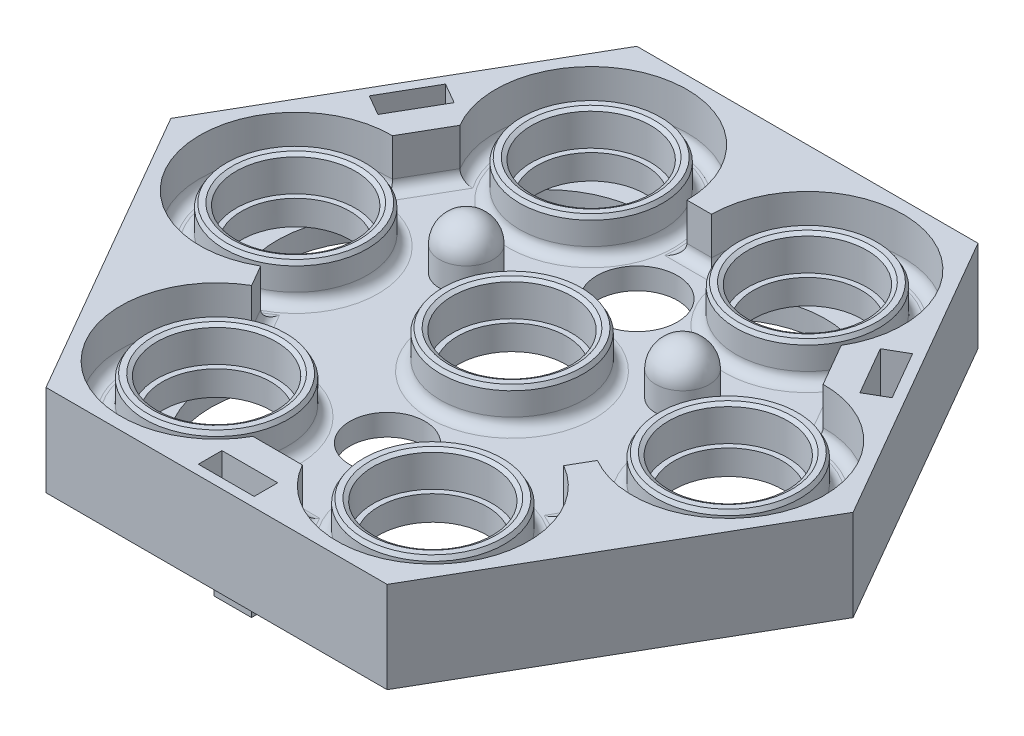
SolidWorks part; units mm, degrees
note: The reader was unsure of these and kept them because the rebuilt part matched: shared geometry of "Sketch3<3>", "Sketch3<4>".
material "PLA"
ref_plane "Front Plane" through (0, 0, 0) normal (0, 0, 1) x (1, 0, 0)
ref_plane "Top Plane" through (0, 0, 0) normal (0, 1, 0) x (1, 0, 0)
ref_plane "Right Plane" through (0, 0, 0) normal (1, 0, 0) x (0, 0, -1)
sketch "Sketch1" plane through (0, 0, 0) normal (0, 1, 0) x (1, 0, 0)
  line L0 (-63.5653, 0) -> (-31.7827, -55.0492)
  line L1 (-29.0764, -19.4379) -> (-31.3719, -15.4619)
  line L2 (-63.5653, 0) -> (-58.1527, 0)
  line L3 (-4.5986, -43.671) -> (4.5986, -43.671)
  line L4 (31.7827, -55.0492) -> (29.0764, -50.3617)
  line L5 (-31.7827, -55.0492) -> (31.7827, -55.0492)
  line L6 (31.7827, 55.0492) -> (-31.7827, 55.0492)
  line L7 (-2.2955, 34.8998) -> (2.2955, 34.8998)
  line L8 (31.7827, 55.0492) -> (29.0764, 50.3617)
  line L9 (-35.5209, 25.818) -> (-40.1195, 17.853)
  line L10 (-63.5653, 0) -> (-58.1527, 0)
  line L11 (-31.7827, 55.0492) -> (-63.5653, 0)
  line L12 (31.7827, -55.0492) -> (63.5653, 0)
  line L13 (31.3719, -15.4619) -> (29.0764, -19.4379)
  line L14 (31.7827, -55.0492) -> (29.0764, -50.3617)
  line L15 (40.1195, 17.853) -> (35.5209, 25.818)
  line L16 (31.7827, 55.0492) -> (29.0764, 50.3617)
  line L17 (63.5653, 0) -> (31.7827, 55.0492)
  arc A0 (-31.3719, -15.4619) -> (-58.1527, 0) centre (-40.2988, 0) cw
  arc A1 (-4.5986, -43.671) -> (-29.0764, -19.4379) centre (-20.1494, -34.8998) cw
  arc A2 (4.5986, -43.671) -> (29.0764, -50.3617) centre (20.1494, -34.8998) ccw
  arc A3 (2.2955, 34.8998) -> (29.0764, 50.3617) centre (20.1494, 34.8998) cw
  arc A4 (-35.5209, 25.818) -> (-2.2955, 34.8998) centre (-20.1494, 34.8998) cw
  arc A5 (-40.1195, 17.853) -> (-58.1527, 0) centre (-40.2988, 0) ccw
  arc A6 (29.0764, -19.4379) -> (29.0764, -50.3617) centre (20.1494, -34.8998) cw
  arc A7 (40.1195, 17.853) -> (31.3719, -15.4619) centre (40.2988, 0) cw
  arc A8 (35.5209, 25.818) -> (29.0764, 50.3617) centre (20.1494, 34.8998) ccw
  point P36 (0, 0)
extrude "Boss-Extrude1" add sketch "Sketch1" against normal blind 28.05 contours A2 L3 A1 L1 A0 L2 L0 L5 L4 | A5 L9 A4 L7 A3 L8 L6 L11 L2 | A8 L15 A7 L13 A6 L4 L12 L17 L8
ref_plane "Plane1" through (0, -20.046, 0) normal (0, 1, 0) x (1, 0, 0)
sketch "Sketch3" plane through (0, -20.046, 0) normal (0, 1, 0) x (1, 0, 0)
  line L0 (-29.0764, -19.4379) -> (-31.3719, -15.4619) construction
  line L1 (-4.5986, -43.671) -> (4.5986, -43.671) construction
  line L2 (31.3719, -15.4619) -> (29.0764, -19.4379) construction
  line L3 (40.1195, 17.853) -> (35.5209, 25.818) construction
  line L4 (-2.2955, 34.8998) -> (2.2955, 34.8998) construction
  line L5 (-35.5209, 25.818) -> (-40.1195, 17.853) construction
  line L6 (-29.0764, -19.4379) -> (-31.3719, -15.4619)
  line L7 (-4.5986, -43.671) -> (4.5986, -43.671)
  line L8 (31.3719, -15.4619) -> (29.0764, -19.4379)
  line L9 (40.1195, 17.853) -> (35.5209, 25.818)
  line L10 (-2.2955, 34.8998) -> (2.2955, 34.8998)
  line L11 (-35.5209, 25.818) -> (-40.1195, 17.853)
  circle A0 centre (-20.1494, 34.8998) radius 11.1
  circle A1 centre (0, 0) radius 11.1
  circle A2 centre (-20.1494, 34.8998) radius 13.35
  circle A3 centre (0, 0) radius 13.35
  circle A4 centre (-20.1494, 34.8998) radius 10.1
  circle A5 centre (0, 0) radius 10.1
  circle A6 centre (20.1494, 34.8998) radius 13.35
  circle A7 centre (20.1494, 34.8998) radius 11.1
  circle A8 centre (20.1494, 34.8998) radius 10.1
  circle A9 centre (40.2988, 0) radius 13.35
  circle A10 centre (40.2988, 0) radius 11.1
  circle A11 centre (40.2988, 0) radius 10.1
  circle A12 centre (20.1494, -34.8998) radius 13.35
  circle A13 centre (20.1494, -34.8998) radius 11.1
  circle A14 centre (20.1494, -34.8998) radius 10.1
  circle A15 centre (-20.1494, -34.8998) radius 13.35
  circle A16 centre (-20.1494, -34.8998) radius 11.1
  circle A17 centre (-20.1494, -34.8998) radius 10.1
  circle A18 centre (-40.2988, 0) radius 13.35
  circle A19 centre (-40.2988, 0) radius 11.1
  circle A20 centre (-40.2988, 0) radius 10.1
  arc A21 (-40.1195, 17.853) -> (-31.3719, -15.4619) centre (-40.2988, 0) ccw construction
  arc A22 (-29.0764, -19.4379) -> (-4.5986, -43.671) centre (-20.1494, -34.8998) ccw construction
  arc A23 (4.5986, -43.671) -> (29.0764, -19.4379) centre (20.1494, -34.8998) ccw construction
  arc A24 (31.3719, -15.4619) -> (40.1195, 17.853) centre (40.2988, 0) ccw construction
  arc A25 (35.5209, 25.818) -> (2.2955, 34.8998) centre (20.1494, 34.8998) ccw construction
  arc A26 (-2.2955, 34.8998) -> (-35.5209, 25.818) centre (-20.1494, 34.8998) ccw construction
  arc A27 (-40.1195, 17.853) -> (-31.3719, -15.4619) centre (-40.2988, 0) ccw
  arc A28 (-29.0764, -19.4379) -> (-4.5986, -43.671) centre (-20.1494, -34.8998) ccw
  arc A29 (4.5986, -43.671) -> (29.0764, -19.4379) centre (20.1494, -34.8998) ccw
  arc A30 (31.3719, -15.4619) -> (40.1195, 17.853) centre (40.2988, 0) ccw
  arc A31 (35.5209, 25.818) -> (2.2955, 34.8998) centre (20.1494, 34.8998) ccw
  arc A32 (-2.2955, 34.8998) -> (-35.5209, 25.818) centre (-20.1494, 34.8998) ccw
  circle A33 centre (0, 0) radius 6.25
  circle A34 centre (-40.2988, 0) radius 6.25
  circle A35 centre (-20.1494, 34.8998) radius 6.25
  circle A36 centre (20.1494, 34.8998) radius 6.25
  circle A37 centre (40.2988, 0) radius 6.25
  circle A38 centre (20.1494, -34.8998) radius 6.25
  circle A39 centre (-20.1494, -34.8998) radius 6.25
  point P46 (0, 0)
  point P71 (0, 0)
  dimension "D1" = 22.2
  dimension "D2" = 22.2
  dimension "D8" = 12.5
  dimension "D9" = 12.5
  dimension "D3" = 2.25
  dimension "D4" = 2.25
  dimension "D5" = 1
  dimension "D6" = 1
  dimension "D7" = 6
  dimension "D10" = 6
extrude "Boss-Extrude2" add sketch "Sketch3" against normal offset from surface (2.494 mm away) 4 contours L10 A32 L11 A27 L6 A28 L7 A29 L8 A30 L9 A31 A2 A3 A6 A9 A12 A15 A18 | A18 A19 | A19 A20 | A20 | A5 | A3 A1 | A1 A5 | A4 | A0 A4 | A2 A0 | A8 | A7 A8 | A6 A7 | A11 | A10 A11 | A9 A10 | A14 | A13 A14 | A12 A13 | A17 | A16 A17 | A15 A16
extrude "Boss-Extrude3" add sketch "Sketch3<3>" along normal blind 0.6 contours A1 A5 | A19 A20 | A0 A4 | A16 A17 | A13 A14 | A7 A8 | A10 A11
sketch "Sketch3<3>" plane through (0, -20.046, 0) normal (0, 1, 0) x (1, 0, 0) same geometry as "Sketch3"
extrude "Boss-Extrude4" add sketch "Sketch3<4>" along normal blind 7 contours A18 A19 | A3 A1 | A2 A0 | A15 A16 | A9 A10 | A12 A13 | A6 A7
sketch "Sketch3<4>" plane through (0, -20.046, 0) normal (0, 1, 0) x (1, 0, 0) same geometry as "Sketch3"
chamfer "Chamfer1" distance 0.75 angle 30 14 edges at (-20.1494, -13.046, -21.5498) (-20.1494, -13.046, -23.7998) (20.1494, -13.046, -23.7998) (20.1494, -13.046, -21.5498) (40.2988, -13.046, 11.1) (40.2988, -13.046, 13.35) (20.1494, -13.046, 48.2498) (20.1494, -13.046, 45.9998) (-20.1494, -13.046, 45.9998) (-20.1494, -13.046, 48.2498) (0, -13.046, 13.35) (0, -13.046, 11.1) (-40.2988, -13.046, 13.35) (-40.2988, -13.046, 11.1)
sketch "Sketch4" plane through (0, -28.05, 0) normal (0, -1, 0) x (1, 0, 0)
  line L0 (-47.674, -27.5246) -> (47.674, 27.5246) construction
  line L1 (-31.7827, -55.0492) -> (-63.5653, 0) construction
  line L2 (31.7827, 55.0492) -> (63.5653, 0) construction
  line L3 (-46.8259, -22.9935) -> (-43.3259, -29.0557)
  line L4 (-46.8259, -22.9935) -> (-44.2278, -21.4935)
  line L5 (-43.3259, -29.0557) -> (-40.7278, -27.5557)
  line L6 (-44.2278, -21.4935) -> (-40.7278, -27.5557)
  line L7 (3.5, 52.0492) -> (-3.5, 52.0492)
  line L8 (3.5, 52.0492) -> (3.5, 49.0492)
  line L9 (3.5, 49.0492) -> (-3.5, 49.0492)
  line L10 (-3.5, 52.0492) -> (-3.5, 49.0492)
  line L11 (43.3259, -29.0557) -> (46.8259, -22.9935)
  line L12 (43.3259, -29.0557) -> (40.7278, -27.5557)
  line L13 (40.7278, -27.5557) -> (44.2278, -21.4935)
  line L14 (46.8259, -22.9935) -> (44.2278, -21.4935)
  point P6 (-42.4778, -24.5246)
  point P21 (0, 0)
  dimension "D1" = 3
  dimension "D2" = 3
  dimension "D4" = 7
  dimension "D3" = 3
extrude "Boss-Extrude5" add sketch "Sketch4" along normal blind 4
sketch "Sketch5" plane through (0, 0, 0) normal (0, 1, 0) x (1, 0, 0)
  line L0 (-63.5653, 0) -> (-31.7827, -55.0492) construction
  line L1 (-30.2241, -17.4499) -> (-47.674, -27.5246) construction
  line L2 (-29.0764, -19.4379) -> (-31.3719, -15.4619) construction
  circle A0 centre (-42.4086, -24.4846) radius 2.175
  circle A1 centre (0, 48.9692) radius 2.175
  circle A2 centre (42.4086, -24.4846) radius 2.175
  point P14 (0, 0)
  dimension "D2" = 4.35
  dimension "D1" = 6.08
  dimension "D3" = 3
extrude "Cut-Extrude1" cut sketch "Sketch5" against normal blind 11.05
sketch "Sketch6" plane through (0, -20.046, 0) normal (0, 1, 0) x (1, 0, 0)
  line L0 (0, 55.0492) -> (0, -55.0492) construction
  line L1 (31.7827, 55.0492) -> (-31.7827, 55.0492) construction
  line L2 (-31.7827, -55.0492) -> (31.7827, -55.0492) construction
  circle A0 centre (0, 23.3222) radius 7.5
  circle A1 centre (0, -23.2122) radius 7
  dimension "D3" = 15
  dimension "D4" = 14
  dimension "D1" = 31.727
  dimension "D2" = 31.837
fillet "Fillet2" radius 2 19 edges at (20.1494, -20.046, 48.2498) (-20.1494, -20.046, 48.2498) (40.2988, -20.046, 13.35) (20.1494, -20.046, -21.5498) (0, -20.046, 13.35) (-40.2988, -20.046, 13.35) (-20.1494, -20.046, -21.5498) (30.2241, -20.046, 17.4499) (57.5673, -20.046, 4.5343) (32.7105, -20.046, 47.5877) (-32.7105, -20.046, 47.5877) (0, -20.046, 43.671) (-30.2241, -20.046, 17.4499) (-57.5673, -20.046, 4.5343) (-37.8202, -20.046, -21.8355) (-24.8569, -20.046, -52.1219) (37.8202, -20.046, -21.8355) (24.8569, -20.046, -52.1219) (0, -20.046, -34.8998)
extrude "Cut-Extrude2" cut sketch "Sketch6" against normal through all contours A1 L0 | L0 A1 | L0 A0 | A0 L0
sketch "Sketch7" plane through (0, 0, 0) normal (0, 1, 0) x (1, 0, 0)
  line L0 (-63.5653, 0) -> (-31.7827, 55.0492)
  line L1 (-31.7827, 55.0492) -> (31.7827, 55.0492)
  line L2 (31.7827, 55.0492) -> (63.5653, 0)
  line L3 (63.5653, 0) -> (31.7827, -55.0492)
  line L4 (31.7827, -55.0492) -> (-31.7827, -55.0492)
  line L5 (-31.7827, -55.0492) -> (-63.5653, 0)
  line L6 (-2.2955, 34.8998) -> (2.2955, 34.8998) construction
  line L7 (35.5209, 25.818) -> (40.1195, 17.853) construction
  line L8 (-4.5986, -43.671) -> (4.5986, -43.671) construction
  line L9 (31.3719, -15.4619) -> (29.0764, -19.4379) construction
  line L10 (-40.1195, 17.853) -> (-35.5209, 25.818) construction
  line L11 (-29.0764, -19.4379) -> (-31.3719, -15.4619) construction
  line L12 (-2.2955, 34.8998) -> (2.2955, 34.8998)
  line L13 (35.5209, 25.818) -> (40.1195, 17.853)
  line L14 (-4.5986, -43.671) -> (4.5986, -43.671)
  line L15 (31.3719, -15.4619) -> (29.0764, -19.4379)
  line L16 (-40.1195, 17.853) -> (-35.5209, 25.818)
  line L17 (-29.0764, -19.4379) -> (-31.3719, -15.4619)
  circle A0 centre (42.4086, -24.4846) radius 2.175 construction
  circle A1 centre (0, 48.9692) radius 2.175 construction
  circle A2 centre (-42.4086, -24.4846) radius 2.175 construction
  circle A3 centre (42.4086, -24.4846) radius 2.175
  circle A4 centre (0, 48.9692) radius 2.175
  circle A5 centre (-42.4086, -24.4846) radius 2.175
  arc A6 (35.5209, 25.818) -> (2.2955, 34.8998) centre (20.1494, 34.8998) ccw construction
  arc A7 (-2.2955, 34.8998) -> (-35.5209, 25.818) centre (-20.1494, 34.8998) ccw construction
  arc A8 (31.3719, -15.4619) -> (40.1195, 17.853) centre (40.2988, 0) ccw construction
  arc A9 (4.5986, -43.671) -> (29.0764, -19.4379) centre (20.1494, -34.8998) ccw construction
  arc A10 (-29.0764, -19.4379) -> (-4.5986, -43.671) centre (-20.1494, -34.8998) ccw construction
  arc A11 (-40.1195, 17.853) -> (-31.3719, -15.4619) centre (-40.2988, 0) ccw construction
  arc A12 (35.5209, 25.818) -> (2.2955, 34.8998) centre (20.1494, 34.8998) ccw
  arc A13 (-2.2955, 34.8998) -> (-35.5209, 25.818) centre (-20.1494, 34.8998) ccw
  arc A14 (31.3719, -15.4619) -> (40.1195, 17.853) centre (40.2988, 0) ccw
  arc A15 (4.5986, -43.671) -> (29.0764, -19.4379) centre (20.1494, -34.8998) ccw
  arc A16 (-29.0764, -19.4379) -> (-4.5986, -43.671) centre (-20.1494, -34.8998) ccw
  arc A17 (-40.1195, 17.853) -> (-31.3719, -15.4619) centre (-40.2988, 0) ccw
extrude "Cut-Extrude3" cut sketch "Sketch7" against normal blind 11.05
sketch "Sketch8" plane through (0, -20.046, 0) normal (0, 1, 0) x (1, 0, 0)
  line L0 (-20.1494, 34.8998) -> (0, 0) construction
  line L1 (0, 0) -> (-40.2988, 0) construction
  line L2 (-40.2988, 0) -> (-20.1494, 34.8998) construction
  circle A0 centre (-40.2988, 0) radius 10.1 construction
  circle A1 centre (0, 0) radius 10.1 construction
  circle A2 centre (-20.1494, 34.8998) radius 10.1 construction
  circle A3 centre (-40.2988, 0) radius 10.1 construction
  circle A4 centre (0, 0) radius 10.1 construction
  circle A5 centre (-20.1494, 34.8998) radius 10.1 construction
  circle A6 centre (-20.1494, 11.6333) radius 11.6333 construction
  circle A7 centre (-20.1494, 11.6333) radius 5
  dimension "D1" = 10
extrude "Boss-Extrude6" add sketch "Sketch8" along normal blind 4.6
sketch "Sketch9" plane through (0, -15.446, 0) normal (0, 1, 0) x (1, 0, 0)
  line L0 (-25.1494, 11.6333) -> (-15.1494, 11.6333)
  line L1 (-15.1494, 11.6333) -> (-10.9418, 11.6333)
  arc A0 (-25.1494, 11.6333) -> (-15.1494, 11.6333) centre (-20.1494, 11.6333) cw
  circle A1 centre (-20.1494, 11.6333) radius 5 construction
  circle A2 centre (-20.1494, 11.6333) radius 5 construction
revolve "Revolve1" add sketch "Sketch9" angle 180 about L1
pattern_circular "CirPattern1" count 2 over 120 about axis through (0, -185.0811, 0) along (0, 1, 0) of "Revolve1", "Boss-Extrude6"
sketch "Sketch10" plane through (0, -11.05, 0) normal (0, 1, 0) x (1, 0, 0)
  line L0 (-5, -49.0492) -> (-5, -53.0492) construction
  line L1 (-5, -49.0492) -> (5, -49.0492) construction
  line L2 (-5, -53.0492) -> (5, -53.0492) construction
  line L3 (5, -49.0492) -> (5, -53.0492) construction
  line L4 (0, 0) -> (0, -55.0492) construction
  line L5 (-31.7827, -55.0492) -> (31.7827, -55.0492) construction
  line L6 (0, -49.0492) -> (0, -53.0492) construction
  line L19 (-5.2, -48.8492) -> (-5.2, -53.2492)
  line L20 (-5.2, -53.2492) -> (5.2, -53.2492)
  line L21 (5.2, -48.8492) -> (5.2, -53.2492)
  line L22 (-5.2, -48.8492) -> (5.2, -48.8492)
  line L23 (-39.7046, 28.9279) -> (-43.5152, 31.1279)
  line L24 (-43.5152, 31.1279) -> (-48.7152, 22.1213)
  line L25 (-44.9046, 19.9213) -> (-48.7152, 22.1213)
  line L26 (-39.7046, 28.9279) -> (-44.9046, 19.9213)
  line L27 (44.9046, 19.9213) -> (48.7152, 22.1213)
  line L28 (48.7152, 22.1213) -> (43.5152, 31.1279)
  line L29 (39.7046, 28.9279) -> (43.5152, 31.1279)
  line L30 (44.9046, 19.9213) -> (39.7046, 28.9279)
  point P25 (0, 0)
  dimension "D1" = 2
  dimension "D2" = 4
  dimension "D3" = 10
  dimension "D4" = 0.2
  dimension "D5" = 3
extrude "Cut-Extrude4" cut sketch "Sketch10" against normal blind 11
sketch "Sketch11" plane through (0, -28.05, 0) normal (0, -1, 0) x (1, 0, 0)
  line L0 (-4.5986, 43.671) -> (4.5986, 43.671)
  line L1 (-31.3719, 15.4619) -> (-29.0764, 19.4379)
  line L2 (-40.1195, -17.853) -> (-35.5209, -25.818)
  line L3 (29.0764, 19.4379) -> (31.3719, 15.4619)
  line L4 (35.5209, -25.818) -> (40.1195, -17.853)
  line L5 (2.2955, -34.8998) -> (-1.9887, -34.8998)
  line L6 (-31.7827, 55.0492) -> (31.7827, 55.0492) construction
  line L7 (31.7827, 55.0492) -> (63.5653, 0) construction
  line L10 (-63.5653, 0) -> (-31.7827, 55.0492) construction
  line L12 (-31.7827, 55.0492) -> (31.7827, 55.0492)
  line L13 (31.7827, 55.0492) -> (63.5653, 0)
  line L14 (31.7827, 55.0492) -> (63.5653, 0)
  line L15 (63.5653, 0) -> (31.7827, -55.0492)
  line L16 (-63.5653, 0) -> (-31.7827, 55.0492)
  line L17 (31.7827, -55.0492) -> (-31.7827, -55.0492)
  line L18 (-35.5209, -25.818) -> (-40.1195, -17.853) construction
  line L19 (40.1195, -17.853) -> (35.5209, -25.818) construction
  line L20 (4.5986, 43.671) -> (-4.5986, 43.671) construction
  line L21 (-29.0764, 19.4379) -> (-31.3719, 15.4619) construction
  line L22 (29.0764, 19.4379) -> (31.3719, 15.4619) construction
  line L23 (2.2955, -34.8998) -> (-2.2955, -34.8998) construction
  line L24 (-40.1195, -17.853) -> (-35.5209, -25.818) construction
  arc A0 (-4.5986, 43.671) -> (-29.0764, 19.4379) centre (-11.2164, 25.8766) ccw
  arc A1 (-31.3719, 15.4619) -> (-40.1195, -17.853) centre (-28.0181, -3.2246) ccw
  arc A2 (29.0764, 19.4379) -> (4.5986, 43.671) centre (11.2164, 25.8766) ccw
  arc A3 (40.1195, -17.853) -> (31.3719, 15.4619) centre (28.0181, -3.2246) ccw
  arc A4 (-35.5209, -25.818) -> (-1.9887, -34.8998) centre (-16.7517, -22.9629) ccw
  arc A5 (2.2955, -34.8998) -> (35.5209, -25.818) centre (16.8016, -22.652) ccw
  point P38 (0, 0)
  point P40 (0, 0)
  point P42 (0, 0)
  point P44 (0, 0)
  point P45 (0, 0)
  point P46 (0, 0)
  point P47 (0, 0)
  point P51 (0, 0)
  point P53 (0, 0)
  point P55 (0, 0)
  point P57 (0, 0)
  point P59 (0, 0)
  point P60 (0, 0)
  point P61 (-40.2811, -17.573)
  point P62 (-39.8885, -18.2531)
  point P66 (0, 0)
  line M19 (3.5, 52.0492) -> (3.5, 49.0492)
  line M20 (3.5, 49.0492) -> (-3.5, 49.0492)
  line M21 (-3.5, 49.0492) -> (-3.5, 52.0492)
  line M22 (-3.5, 52.0492) -> (3.5, 52.0492)
  line M23 (31.7827, -55.0492) -> (63.5653, 0)
  line M24 (63.5653, 0) -> (31.7827, 55.0492)
  line M25 (31.7827, 55.0492) -> (-31.7827, 55.0492)
  line M26 (-31.7827, 55.0492) -> (-63.5653, 0)
  line M27 (-63.5653, 0) -> (-31.7827, -55.0492)
  line M28 (-31.7827, -55.0492) -> (31.7827, -55.0492)
  line M29 (2.2955, -34.8998) -> (-2.2955, -34.8998)
  arc M30 (-2.2955, -34.8998) -> (-35.5209, -25.818) centre (-20.1494, -34.8998) cw
  line M31 (-35.5209, -25.818) -> (-40.1195, -17.853)
  arc M32 (-40.1195, -17.853) -> (-31.3719, 15.4619) centre (-40.2988, 0) cw
  line M33 (-31.3719, 15.4619) -> (-29.0764, 19.4379)
  arc M34 (-29.0764, 19.4379) -> (-4.5986, 43.671) centre (-20.1494, 34.8998) cw
  line M35 (-4.5986, 43.671) -> (4.5986, 43.671)
  arc M36 (4.5986, 43.671) -> (29.0764, 19.4379) centre (20.1494, 34.8998) cw
  line M37 (29.0764, 19.4379) -> (31.3719, 15.4619)
  arc M38 (31.3719, 15.4619) -> (40.1195, -17.853) centre (40.2988, 0) cw
  line M39 (40.1195, -17.853) -> (35.5209, -25.818)
  arc M40 (35.5209, -25.818) -> (2.2955, -34.8998) centre (20.1494, -34.8998) cw
  line M41 (43.3259, -29.0557) -> (40.7278, -27.5557)
  line M42 (40.7278, -27.5557) -> (44.2278, -21.4935)
  line M43 (44.2278, -21.4935) -> (46.8259, -22.9935)
  line M44 (46.8259, -22.9935) -> (43.3259, -29.0557)
  line M45 (-46.8259, -22.9935) -> (-44.2278, -21.4935)
  line M46 (-44.2278, -21.4935) -> (-40.7278, -27.5557)
  line M47 (-40.7278, -27.5557) -> (-43.3259, -29.0557)
  line M48 (-43.3259, -29.0557) -> (-46.8259, -22.9935)
extrude "Boss-Extrude7" add sketch "Sketch11" against normal up to surface (4 mm away) contours A4 M28 M23 M24 M25 M26 M27 M30 M31 M32 M33 M34 M35 M36 M37 M38 M39 M40 M29 M44 M41 M42 M43 M48 M45 M46 M47 M22 M19 M20 M21 | A4 M30 | A1 M32 | A0 M34 | A2 M36 | A3 M38 | A5 M40 up to face at (0, -24.05, 30.2122)
equation "\"height_diff_support_plate_og_bushing\"=11.05"
equation "\"D1@Cut-Extrude3\"=\"height_diff_support_plate_og_bushing\""
equation "\"D1@Cut-Extrude1\"=\"height_diff_support_plate_og_bushing\""
